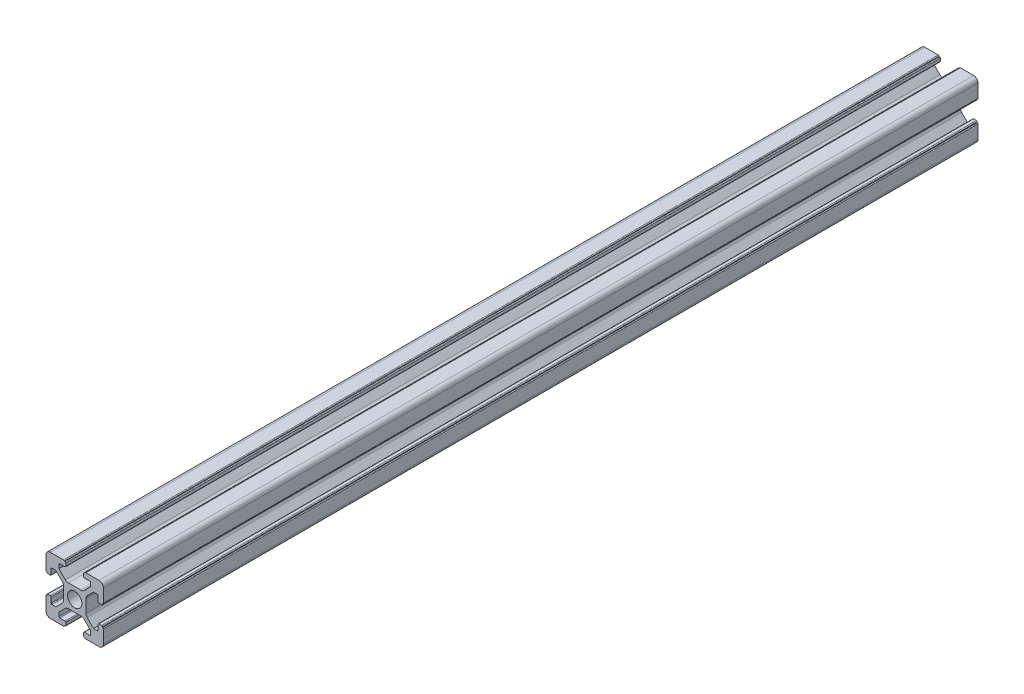
SolidWorks part; units mm, degrees
material "1060 Alloy"
ref_plane "Front Plane" through (0, 0, 0) normal (0, 0, 1) x (1, 0, 0)
ref_plane "Top Plane" through (0, 0, 0) normal (0, 1, 0) x (1, 0, 0)
ref_plane "Right Plane" through (0, 0, 0) normal (1, 0, 0) x (0, 0, -1)
sketch "Sketch1" plane through (0, 0, 0) normal (0, 0, 1) x (1, 0, 0)
  line L0 (3.8995, 3.9005) -> (10.4604, 10.4604) construction
  line L2 (-3.9002, 2.2177) -> (-3.9002, -2.2208)
  line L5 (-3.9005, 3.899) -> (3.9001, -3.8986) construction
  line L6 (-3.9, -3.901) -> (3.8995, 3.9005) construction
  line L7 (-0.0002, 10) -> (-0.0002, -9.9996) construction
  line L8 (-0.0002, -9.9996) -> (-0.0002, 10) construction
  line L9 (5.5006, 6.5619) -> (3.2793, 4.3405)
  line L14 (-10.0002, 9.9996) -> (9.9994, -10) construction
  line L15 (-9.9999, -10.0001) -> (9.9998, 10) construction
  line L16 (6.5613, 5.5012) -> (4.3401, 3.28)
  line L17 (-5.5002, 6.5603) -> (-3.279, 4.3391)
  line L18 (-6.5609, 5.4996) -> (-4.3395, 3.2783)
  line L19 (7.9206, 5.5012) -> (6.5613, 5.5012)
  line L20 (8.2006, 3.3812) -> (8.2006, 5.2212)
  line L21 (9.4206, 3.1012) -> (8.4806, 3.1012)
  line L22 (9.7006, 3.6012) -> (9.7006, 3.3812)
  line L23 (-8.5002, 9.9996) -> (-3.8802, 9.9996)
  line L24 (-3.6002, 9.7196) -> (-3.6002, 9.6996)
  line L25 (-3.6002, 9.6996) -> (-3.3802, 9.6996)
  line L26 (-3.1002, 9.4196) -> (-3.1002, 8.4796)
  line L27 (-3.3802, 8.1996) -> (-5.2202, 8.1996)
  line L28 (-5.5002, 7.9196) -> (-5.5002, 6.5603)
  line L29 (-7.9202, 5.4996) -> (-6.5609, 5.4996)
  line L30 (-8.2002, 3.3796) -> (-8.2002, 5.2196)
  line L31 (-9.4202, 3.0996) -> (-8.4802, 3.0996)
  line L32 (-9.7202, 3.5996) -> (-9.7002, 3.5996)
  line L33 (-9.7002, 3.5996) -> (-9.7002, 3.3796)
  line L34 (-10.0002, 8.4996) -> (-10.0002, 3.8796)
  line L35 (10.0006, 8.5012) -> (10.0006, 3.8812)
  line L36 (8.5006, 10.0012) -> (3.8806, 10.0012)
  line L37 (3.6006, 9.7012) -> (3.3806, 9.7012)
  line L38 (3.1006, 9.4212) -> (3.1006, 8.4812)
  line L39 (3.3806, 8.2012) -> (5.2206, 8.2012)
  line L40 (5.5006, 7.9212) -> (5.5006, 6.5619)
  line L41 (6.5629, -5.4996) -> (4.3415, -3.2783)
  line L42 (5.5022, -6.5603) -> (3.281, -4.3391)
  line L43 (5.5022, -7.9196) -> (5.5022, -6.5603)
  line L44 (3.3822, -8.1996) -> (5.2222, -8.1996)
  line L45 (3.1022, -9.4196) -> (3.1022, -8.4796)
  line L46 (3.6022, -9.6996) -> (3.3822, -9.6996)
  line L47 (8.5022, -9.9996) -> (3.8822, -9.9996)
  line L48 (10.0022, -8.4996) -> (10.0022, -3.8796)
  line L49 (9.7022, -3.5996) -> (9.7022, -3.3796)
  line L50 (9.4222, -3.0996) -> (8.4822, -3.0996)
  line L51 (8.2022, -3.3796) -> (8.2022, -5.2196)
  line L52 (7.9222, -5.4996) -> (6.5629, -5.4996)
  line L53 (-5.4986, -6.5619) -> (-3.2773, -4.3405)
  line L54 (-6.5593, -5.5012) -> (-4.3395, -3.2814)
  line L55 (-7.9186, -5.5012) -> (-6.5593, -5.5012)
  line L56 (-8.1986, -3.3812) -> (-8.1986, -5.2212)
  line L57 (-9.4186, -3.1012) -> (-8.4786, -3.1012)
  line L58 (-9.6986, -3.6012) -> (-9.6986, -3.3812)
  line L59 (-9.9986, -8.5012) -> (-9.9986, -3.8812)
  line L60 (-8.4986, -10.0012) -> (-3.8786, -10.0012)
  line L61 (-3.5986, -9.7012) -> (-3.3786, -9.7012)
  line L62 (-3.0986, -9.4212) -> (-3.0986, -8.4812)
  line L63 (-3.3786, -8.2012) -> (-5.2186, -8.2012)
  line L64 (-5.4986, -7.9212) -> (-5.4986, -6.5619)
  line L65 (-2.233, 3.8998) -> (2.2187, 3.9012)
  line L66 (3.9008, 2.234) -> (3.9022, -2.2177)
  line L67 (2.235, -3.8998) -> (-2.2167, -3.9012)
  line L68 (3.6006, 9.7212) -> (3.6006, 9.6996)
  line L69 (9.7006, 3.6012) -> (9.7206, 3.6012)
  line L70 (-9.6986, -3.6012) -> (-9.7186, -3.6012)
  line L71 (-3.5986, -9.7012) -> (-3.5986, -9.7212)
  line L72 (3.6022, -9.6996) -> (3.6022, -9.7196)
  line L73 (9.7222, -3.5996) -> (9.7022, -3.5996)
  arc A0 (-3.6002, 9.7196) -> (-3.8802, 9.9996) centre (-3.8802, 9.7196) ccw
  arc A1 (-3.3802, 9.6996) -> (-3.1002, 9.4196) centre (-3.3802, 9.4196) cw
  arc A2 (-3.1002, 8.4796) -> (-3.3802, 8.1996) centre (-3.3802, 8.4796) cw
  arc A3 (-10.0002, 8.4996) -> (-8.5002, 9.9996) centre (-8.5002, 8.4996) cw
  arc A4 (-8.2002, 3.3796) -> (-8.4802, 3.0996) centre (-8.4802, 3.3796) cw
  arc A5 (-9.4202, 3.0996) -> (-9.7002, 3.3796) centre (-9.4202, 3.3796) cw
  arc A6 (-9.7202, 3.5996) -> (-10.0002, 3.8796) centre (-9.7202, 3.8796) cw
  arc A7 (-3.279, 4.3391) -> (-2.233, 3.8998) centre (-2.2183, 5.3997) ccw
  arc A8 (-4.3395, 3.2783) -> (-3.9002, 2.2177) centre (-5.4002, 2.2177) cw
  arc A9 (-7.9202, 5.4996) -> (-8.2002, 5.2196) centre (-7.9202, 5.2196) ccw
  arc A10 (-5.2202, 8.1996) -> (-5.5002, 7.9196) centre (-5.2202, 7.9196) ccw
  arc A12 (-4.3395, -3.2814) -> (-3.9002, -2.2208) centre (-5.4002, -2.2208) ccw
  arc A13 (8.2006, 5.2212) -> (7.9206, 5.5012) centre (7.9206, 5.2212) ccw
  arc A14 (8.4806, 3.1012) -> (8.2006, 3.3812) centre (8.4806, 3.3812) cw
  arc A15 (9.7006, 3.3812) -> (9.4206, 3.1012) centre (9.4206, 3.3812) cw
  arc A16 (9.7206, 3.6012) -> (10.0006, 3.8812) centre (9.7206, 3.8812) ccw
  arc A17 (8.5006, 10.0012) -> (10.0006, 8.5012) centre (8.5006, 8.5012) cw
  arc A18 (3.6006, 9.7212) -> (3.8806, 10.0012) centre (3.8806, 9.7212) cw
  arc A19 (3.1006, 9.4212) -> (3.3806, 9.7012) centre (3.3806, 9.4212) cw
  arc A20 (3.3806, 8.2012) -> (3.1006, 8.4812) centre (3.3806, 8.4812) cw
  arc A21 (5.5006, 7.9212) -> (5.2206, 8.2012) centre (5.2206, 7.9212) ccw
  arc A22 (3.2793, 4.3405) -> (2.2187, 3.9012) centre (2.2187, 5.4012) cw
  arc A23 (4.3401, 3.28) -> (3.9008, 2.234) centre (5.4007, 2.2193) ccw
  arc A25 (5.2222, -8.1996) -> (5.5022, -7.9196) centre (5.2222, -7.9196) ccw
  arc A26 (3.1022, -8.4796) -> (3.3822, -8.1996) centre (3.3822, -8.4796) cw
  arc A27 (3.3822, -9.6996) -> (3.1022, -9.4196) centre (3.3822, -9.4196) cw
  arc A28 (3.6022, -9.7196) -> (3.8822, -9.9996) centre (3.8822, -9.7196) ccw
  arc A29 (10.0022, -8.4996) -> (8.5022, -9.9996) centre (8.5022, -8.4996) cw
  arc A30 (9.7222, -3.5996) -> (10.0022, -3.8796) centre (9.7222, -3.8796) cw
  arc A31 (9.4222, -3.0996) -> (9.7022, -3.3796) centre (9.4222, -3.3796) cw
  arc A32 (8.2022, -3.3796) -> (8.4822, -3.0996) centre (8.4822, -3.3796) cw
  arc A33 (7.9222, -5.4996) -> (8.2022, -5.2196) centre (7.9222, -5.2196) ccw
  arc A34 (4.3415, -3.2783) -> (3.9022, -2.2177) centre (5.4022, -2.2177) cw
  arc A35 (3.281, -4.3391) -> (2.235, -3.8998) centre (2.2203, -5.3997) ccw
  circle A36 centre (0.001, -0.001) radius 2.5 construction
  arc A37 (-8.1986, -5.2212) -> (-7.9186, -5.5012) centre (-7.9186, -5.2212) ccw
  arc A38 (-8.4786, -3.1012) -> (-8.1986, -3.3812) centre (-8.4786, -3.3812) cw
  arc A39 (-9.6986, -3.3812) -> (-9.4186, -3.1012) centre (-9.4186, -3.3812) cw
  arc A40 (-9.7186, -3.6012) -> (-9.9986, -3.8812) centre (-9.7186, -3.8812) ccw
  arc A41 (-8.4986, -10.0012) -> (-9.9986, -8.5012) centre (-8.4986, -8.5012) cw
  arc A42 (-3.5986, -9.7212) -> (-3.8786, -10.0012) centre (-3.8786, -9.7212) cw
  arc A43 (-3.0986, -9.4212) -> (-3.3786, -9.7012) centre (-3.3786, -9.4212) cw
  arc A44 (-3.3786, -8.2012) -> (-3.0986, -8.4812) centre (-3.3786, -8.4812) cw
  arc A45 (-5.4986, -7.9212) -> (-5.2186, -8.2012) centre (-5.2186, -7.9212) ccw
  arc A46 (-3.2773, -4.3405) -> (-2.2167, -3.9012) centre (-2.2167, -5.4012) cw
  arc A48 (-4.3381, -3.28) -> (-3.8988, -2.234) centre (-5.3987, -2.2193) ccw [skipped]
  point P0 (0, 0)
  point P9 (-0.0002, 0.0002)
  point P12 (-0.0003, -0.0003)
  point P43 (-3.6002, 9.9996)
  point P46 (-3.1002, 9.6996)
  point P49 (-3.1002, 8.1996)
  point P55 (-8.2002, 3.0996)
  point P58 (-9.7002, 3.0996)
  point P61 (-10.0002, 3.5996)
  point P64 (-2.8395, 3.8996)
  point P67 (-3.9002, 2.839)
  point P70 (-8.2002, 5.4996)
  point P73 (-5.5002, 8.1996)
  point P184 (0.001, 0)
  dimension "D14" = 0.28
  dimension "D15" = 0.28
  dimension "D16" = 0.28
  dimension "D17" = 1.5
  dimension "D18" = 0.28
  dimension "D19" = 1.5
  dimension "D20" = 1.5
  dimension "D21" = 0.28
  dimension "D23" = 5
  dimension "D27" = 1.5
  dimension "D1" = 7.8
  dimension "D2" = 7.8
  dimension "D3" = 3.1
  dimension "D4" = 3.6
  dimension "D5" = 20
  dimension "D6" = 20
  dimension "D7" = 0.75
  dimension "D8" = 1.8
  dimension "D9" = 5.5
  dimension "D10" = 6.4
  dimension "D11" = 6.4
  dimension "D12" = 3.7627
  dimension "D13" = 0.3
  dimension "D24" = 4.62
  dimension "D25" = 3.9005
  dimension "D26" = 7.801
  dimension "D22" = 4
extrude "Boss-Extrude1" add sketch "Sketch1" along normal blind 304.8 contours L53 A46 L67 A35 L42 L43 A25 L44 A26 L45 A27 L46 L72 A28 L47 A29 L48 A30 L73 L49 A31 L50 A32 L51 A33 L52 L41 A34 L66 A23 L16 L19 A13 L20 A14 L21 A15 L22 L69 A16 L35 A17 L36 A18 L68 L37 A19 L38 A20 region at (0.0009, 0, 0)
sketch3d "3DSketch2"
  circle A0 centre (0, 0, 0) radius 2.5
  point P2 (0, 0, 2.5)
extrude "Cut-Extrude1" cut sketch "3DSketch2" along direction (0, 0, 1) on the side of the normal through all contours A0
